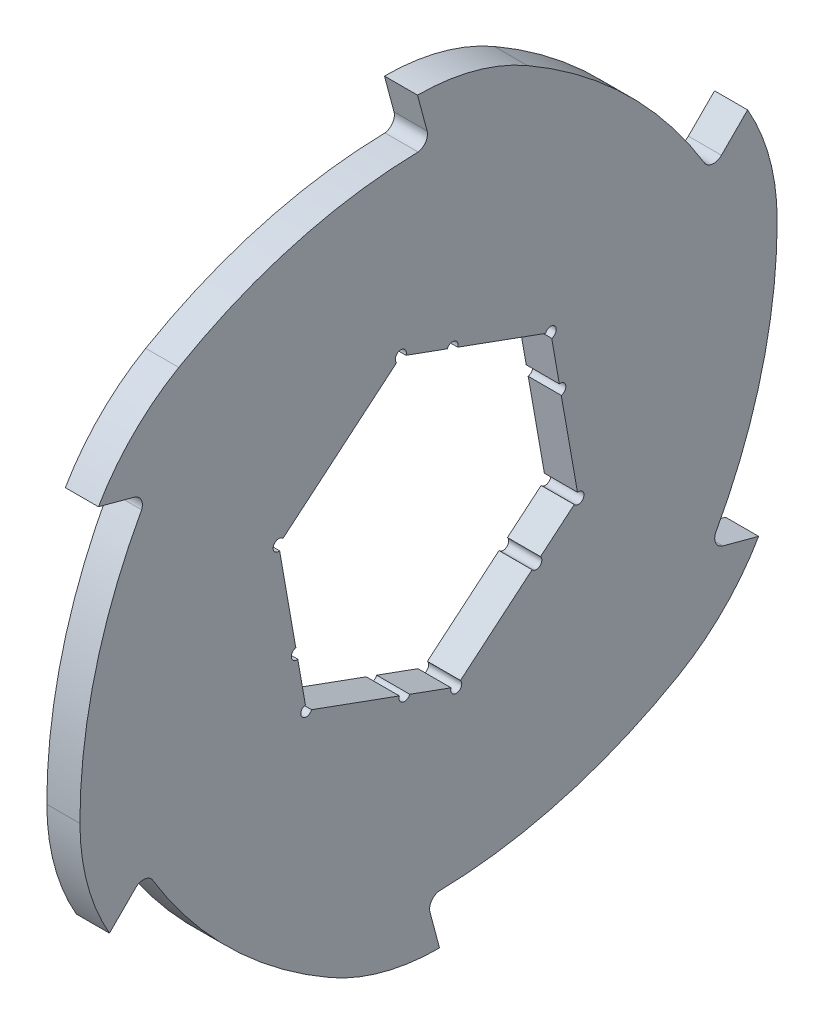
SolidWorks part; units mm, degrees
note: '?' marks a value the reader was unsure of.
material "1.0037 (S235JR)"
ref_plane "Alzado" through (0, 0, 0) normal (0, 0, 1) x (1, 0, 0)
ref_plane "Planta" through (0, 0, 0) normal (0, 1, 0) x (1, 0, 0)
ref_plane "Vista lateral" through (0, 0, 0) normal (1, 0, 0) x (0, 0, -1)
sketch "Sketch1" plane through (0, 0, 0) normal (1, 0, 0) x (0, 0, -1)
  line L0 (-56.6126, 0) -> (65.57, 0) construction
  line L1 (22.158, 18.5928) -> (-5.0228, 28.4858)
  line L2 (-5.0228, 28.4858) -> (-27.1808, 9.893)
  line L3 (-27.1808, 9.893) -> (-22.158, -18.5928)
  line L4 (-22.158, -18.5928) -> (5.0228, -28.4858)
  line L5 (5.0228, -28.4858) -> (27.1808, -9.893)
  line L6 (27.1808, -9.893) -> (22.158, 18.5928)
  circle A0 centre (0, 0) radius 25.05 construction
  circle A1 centre (0, 0) radius 59
  dimension "D2" = 118
  dimension "D1" = 50.1
  dimension "D3" = 20
extrude "Extrude1" add sketch "Sketch1" along normal mid plane 6
ref_axis "Axis1" through (-5.5, 0, 0) along (1, 0, 0)?
sketch "Sketch2" plane through (0, 0, 0) normal (1, 0, 0) x (0, 0, -1)
  line L0 (-2, 67.9618) -> (-0.2627, 61.4781)
  line L1 (0, 0) -> (0, 77.6328) construction
  line L4 (-2.1226, 58.9618) -> (0, 0) construction
  circle A0 centre (0, 0) radius 59 construction
  arc A1 (-2, 67.9618) -> (17.9271, 62.6448) centre (-2, 27.9618) cw
  arc A3 (51.2137, 29.2943) -> (-2.1226, 58.9618) centre (0, 0) ccw
  arc A4 (-0.2627, 61.4781) -> (-2.1226, 58.9618) centre (-2.1946, 60.9605) cw
  arc A5 (17.9271, 62.6448) -> (51.2137, 29.2943) centre (-26.9089, -15.3919) cw
  point P10 (-2, 67.9618)
  dimension "D2" = 40
  dimension "D4" = 2
  dimension "D3" = 9
  dimension "D6" = 90
  dimension "D1" = 15
  dimension "D5" = 2
extrude "Extrude2" add sketch "Sketch2" against normal mid plane 6
fillet "Fillet1" [suppressed] radius 0.6
pattern_circular "CirPattern1" count 6 over 360 about axis through (0, 0, 0) along (1, 0, 0) of "Extrude2", "Fillet1"
sketch "Sketch4" [suppressed] plane through (3, 0, 0) normal (1, 0, 0) x (0, 0, -1)
  circle A0 centre (0, 0) radius 67.9646 construction
  dimension "D1" = 135.9291
hole_wizard "Ø2.0 (2) Diameter Hole1" positions "Sketch5" profile "Sketch7" hole size "Ø2.0" standard "ISO" end condition up to next
sketch "Sketch5" plane through (3, 0, 0) normal (1, 0, 0) x (0, 0, -1)
  point P0 (-5.0228, 28.4858)
  point P7 (22.158, 18.5928)
  point P8 (27.1808, -9.893)
  point P9 (5.0228, -28.4858)
  point P10 (-22.158, -18.5928)
  point P11 (-27.1808, 9.893)
  dimension "D1" = 6
sketch "Sketch7" plane through (3, 28.4858, 5.0228) normal (0, 1, 0) x (0, 0, -1)
  line L0 (0, 0) -> (0, 6)
  line L1 (0, 6) -> (1, 6)
  line L2 (1, 6) -> (1, 0)
  line L5 (1, 0) -> (0, 0)
  line L11 (0, -6.35) -> (0, 107.95) construction
  dimension "Diámetro de taladro hasta el siguiente" = 2
  dimension "Profundidad de taladro hasta el siguiente" = 6
hole_wizard "Ø2.0 (2) Diameter Hole3" positions "Sketch10" profile "Sketch11" hole size "Ø2.0" standard "ISO" end condition up to next
sketch "Sketch10" plane through (3, 0, 0) normal (1, 0, 0) x (0, 0, -1)
  line L0 (-4.0831, 28.1438) -> (4.3507, 25.0741) construction
  line L1 (21.2183, 18.9348) -> (-4.0831, 28.1438) construction
  line L2 (4.3507, 25.0741) -> (12.7845, 22.0045) construction
  line L3 (12.7845, 22.0045) -> (21.2183, 18.9348) construction
  point P2 (4.3507, 25.0741)
sketch "Sketch11" plane through (3, 25.0741, -4.3507) normal (0, 1, 0) x (0, 0, -1)
  line L0 (0, 0) -> (0, 6.001)
  line L1 (0, 6.001) -> (1, 6.001)
  line L2 (1, 6.001) -> (1, 0)
  line L5 (1, 0) -> (0, 0)
  line L11 (0, -6.35) -> (0, 107.95) construction
  dimension "Diámetro de taladro hasta el siguiente" = 2
  dimension "Profundidad de taladro hasta el siguiente" = 6.001
hole_wizard "Ø2.0 (2) Diameter Hole4" [suppressed] positions "Sketch12" profile "Sketch13" hole size "Ø2.0" standard "ISO"
sketch "Sketch12" plane through (3, 0, 0) normal (1, 0, 0) x (0, 0, -1)
  line L0 (13.4626, 25.05) -> (-3.4875, 25.05) construction
  point P0 (4.9875, 25.05)
sketch "Sketch13" plane through (3, 25.05, -4.9875) normal (0, 1, 0) x (0, 0, -1)
  line L0 (0, 0) -> (0, 6)
  line L1 (0, 6) -> (1, 6)
  line L2 (1, 6) -> (1, 0)
  line L5 (1, 0) -> (0, 0)
  line L11 (0, -6.35) -> (0, 107.95) construction
  dimension "Diámetro de taladro hasta el siguiente" = 2
  dimension "Profundidad de taladro hasta el siguiente" = 6
pattern_circular "CirPattern2" count 5 every 60 about axis through (0, 0, 0) along (1, 0, 0) of "Ø2.0 (2) Diameter Hole3"
pattern_circular "CirPattern3" [suppressed] count 1 every? 60? about axis through (-5.5, 0, 0) along (1, 0, 0)
equation "\"D1@Extrude2\"=\"D1@Extrude1\""
